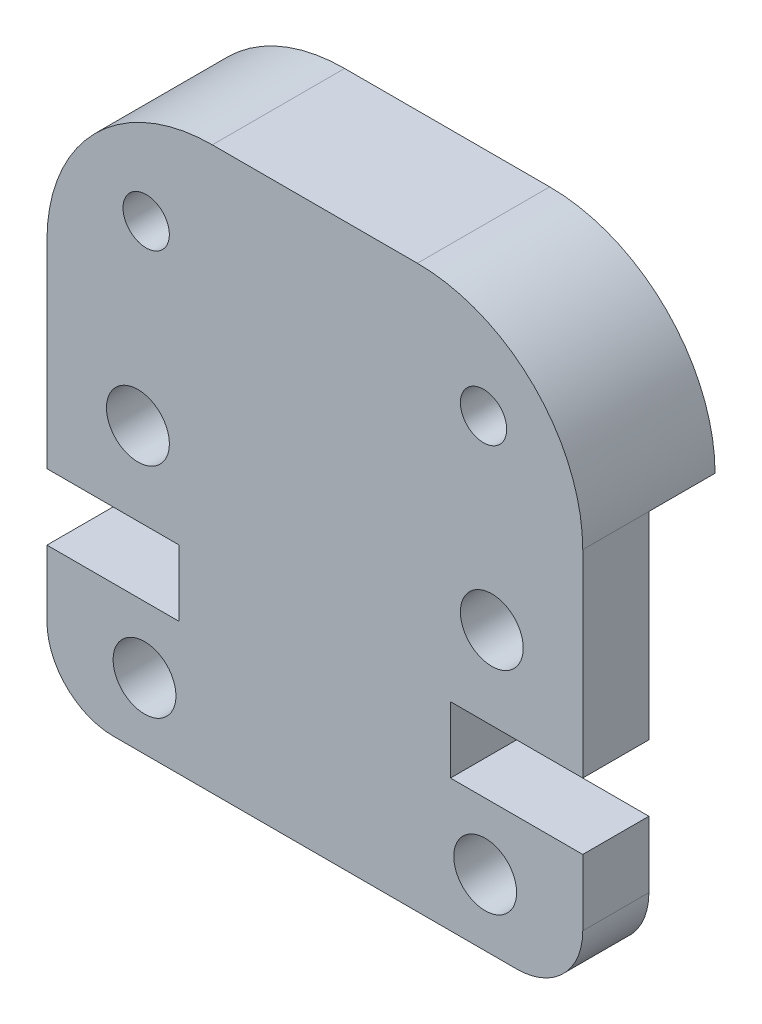
SolidWorks part; units mm, degrees
ref_plane "Front Plane" through (0, 0, 0) normal (0, 0, 1) x (1, 0, 0)
ref_plane "Top Plane" through (0, 0, 0) normal (0, 1, 0) x (1, 0, 0)
ref_plane "Right Plane" through (0, 0, 0) normal (1, 0, 0) x (0, 0, -1)
sketch "Sketch1" plane through (0, 0, 0) normal (0, 0, 1) x (1, 0, 0)
  line L0 (0, 16.98) -> (0, 0) construction
  line L1 (3.1, 16.98) -> (-3.1, 16.98)
  line L2 (6.1, 0) -> (-6.1, 0)
  line L3 (-8.1, 6) -> (-4.1, 6)
  line L4 (-4.1, 6) -> (-4.1, 4)
  line L5 (-4.1, 4) -> (-8.1, 4)
  line L6 (-8.1, 2) -> (-8.1, 4)
  line L7 (8.1, 11.98) -> (8.1, 6)
  line L8 (-8.1, 11.98) -> (-8.1, 6)
  line L24 (8.1, 2) -> (8.1, 4)
  line L27 (4.1, 4) -> (8.1, 4)
  line L30 (4.1, 6) -> (4.1, 4)
  line L31 (8.1, 6) -> (4.1, 6)
  circle A0 centre (-5.15, 2) radius 0.95
  circle A1 centre (-5.1, 13.98) radius 0.7
  arc A2 (-8.1, 11.98) -> (-3.1, 16.98) centre (-3.1, 11.98) cw
  arc A3 (-6.1, 0) -> (-8.1, 2) centre (-6.1, 2) cw
  circle A4 centre (-5.35, 8.5) radius 0.95
  circle A10 centre (5.35, 8.5) radius 0.95
  arc A12 (6.1, 0) -> (8.1, 2) centre (6.1, 2) ccw
  arc A14 (8.1, 11.98) -> (3.1, 16.98) centre (3.1, 11.98) ccw
  circle A16 centre (5.1, 13.98) radius 0.7
  circle A18 centre (5.15, 2) radius 0.95
  dimension "D1" = 1.9
  dimension "D2" = 1.4
  dimension "D5" = 5
  dimension "D6" = 6.1
  dimension "D4" = 2
  dimension "D3" = 16.98
  dimension "D7" = 3
  dimension "D10" = 8.5
  dimension "D9" = 2.75
  dimension "D8" = 3
extrude "Boss-Extrude1" add sketch "Sketch1" along normal blind 4
sketch "Sketch2" plane through (0, 0, 0) normal (0, 0, 1) x (1, 0, 0)
  line L0 (-8.1, 0) -> (8.1, 0)
  line L1 (8.1, 0) -> (8.1, 11.98)
  line L2 (8.1, 11.98) -> (-8.1, 11.98)
  line L3 (-8.1, 11.98) -> (-8.1, 0)
extrude "Cut-Extrude1" cut sketch "Sketch2" along normal blind 2
equation "\"D6@Sketch1\"= ( \"fingerWidth@parametersSketch@prostheticParameters.SLDPRT\" - 4 ) / 2'Finger Width - Radius"
equation "\"D3@Sketch1\"= ( \"HL@parametersSketch@prostheticParameters.SLDPRT\" * 0.108 ) - 3 'DIP Legth-Sil. Sh. DIP"
equation "\"D1@Sketch1\"= 1.5 + \"tol1@parametersSketch@prostheticParameters.SLDPRT\""
equation "\"D2@Sketch1\"= 1 + \"tol1@parametersSketch@prostheticParameters.SLDPRT\""
